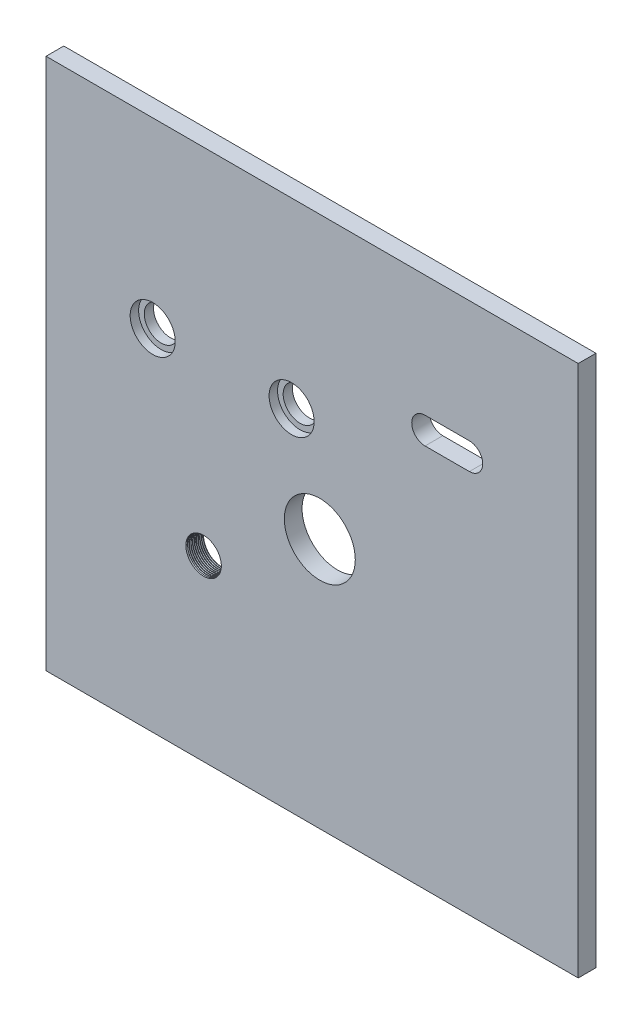
SolidWorks part; units mm, degrees
ref_plane "Front" through (0, 0, 0) normal (0, 0, 1) x (1, 0, 0)
ref_plane "Top" through (0, 0, 0) normal (0, 1, 0) x (1, 0, 0)
ref_plane "Right" through (0, 0, 0) normal (1, 0, 0) x (0, 0, -1)
sketch "Sketch1" plane through (0, 0, 0) normal (0, 0, 1) x (1, 0, 0)
  line L1 (0, 0) -> (-300, 0)
  line L2 (0, 0) -> (0, 300)
  line L3 (0, 300) -> (-300, 300)
  line L4 (-300, 0) -> (-300, 300)
  dimension "D1" = 300
  dimension "D2" = 300
extrude "Boss-Extrude1" add sketch "Sketch1" along normal blind 10
hole_wizard "CBORE for 3/4 Standard Leader Pin1" positions "Sketch2" profile "Sketch3" counterbore size "3/4" standard "DME" end condition through all
sketch "Sketch2" plane through (0, 0, 10) normal (0, 0, 1) x (1, 0, 0)
  point P0 (-239.8751, 197.1622)
  point P2 (-161.5681, 197.1622)
sketch "Sketch3" plane through (-239.8751, 197.1622, 10) normal (1, 0, 0) x (0, -1, 0)
  line L0 (0, 0) -> (0, 10)
  line L1 (0, 10) -> (9.525, 10)
  line L3 (9.525, 10) -> (9.525, 4.7625)
  line L4 (9.525, 4.7625) -> (12.7, 4.7625)
  line L5 (12.7, 4.7625) -> (12.7, 0)
  line L7 (12.7, 0) -> (0, 0)
  line L11 (0, -6.35) -> (0, 107.95) construction
  dimension "Thru Hole Dia." = 19.05
  dimension "Thru Hole Depth" = 10
  dimension "C'Bore Dia." = 25.4
  dimension "C'Bore Depth" = 4.7625
sketch "Sketch4" plane through (0, 0, 10) normal (0, 0, 1) x (1, 0, 0)
  line L0 (-86.3508, 224.0698) -> (-61.3508, 224.0698) construction
  line L1 (-86.3508, 231.5698) -> (-61.3508, 231.5698)
  line L2 (-86.3508, 216.5698) -> (-61.3508, 216.5698)
  circle A0 centre (-211.1774, 100.5637) radius 10
  circle A1 centre (-145.6743, 141.3487) radius 20
  arc A2 (-86.3508, 231.5698) -> (-86.3508, 216.5698) centre (-86.3508, 224.0698) ccw
  arc A3 (-61.3508, 216.5698) -> (-61.3508, 231.5698) centre (-61.3508, 224.0698) ccw
  point P6 (-73.8508, 224.0698)
extrude "Cut-Extrude1" cut sketch "Sketch4" against normal blind 10
thread "Thread1" pitch 1 method cut profile "Thread Profile1" start angle 0, offset 0, length 10, pitch 1, diameter 20
ref_plane "Plane1" through (-221.1774, 100.5637, 10) normal (0, -1, 0) x (-1, 0, 0)
sketch "Thread Profile1" plane through (-221.1774, 100.5637, 10) normal (0, -1, 0) x (-1, 0, 0)
  line L0 (0, 0) -> (0, 1) construction
  line L1 (0, 0) -> (0.5413, 0.3125)
  line L2 (0.5413, 0.3125) -> (0.5413, 0.4375)
  line L3 (0.5413, 0.4375) -> (0, 0.75)
  line L4 (0.5413, 0.375) -> (0, 0.375) construction
  line L11 (0, 0) -> (0, 0.75)
  point P2 (0, 0)
  dimension "Pitch" = 1
  dimension "Profile_Angle" = 60
  dimension "Profile_Land" = 0.125
  dimension "Profile_Height" = 0.5413
